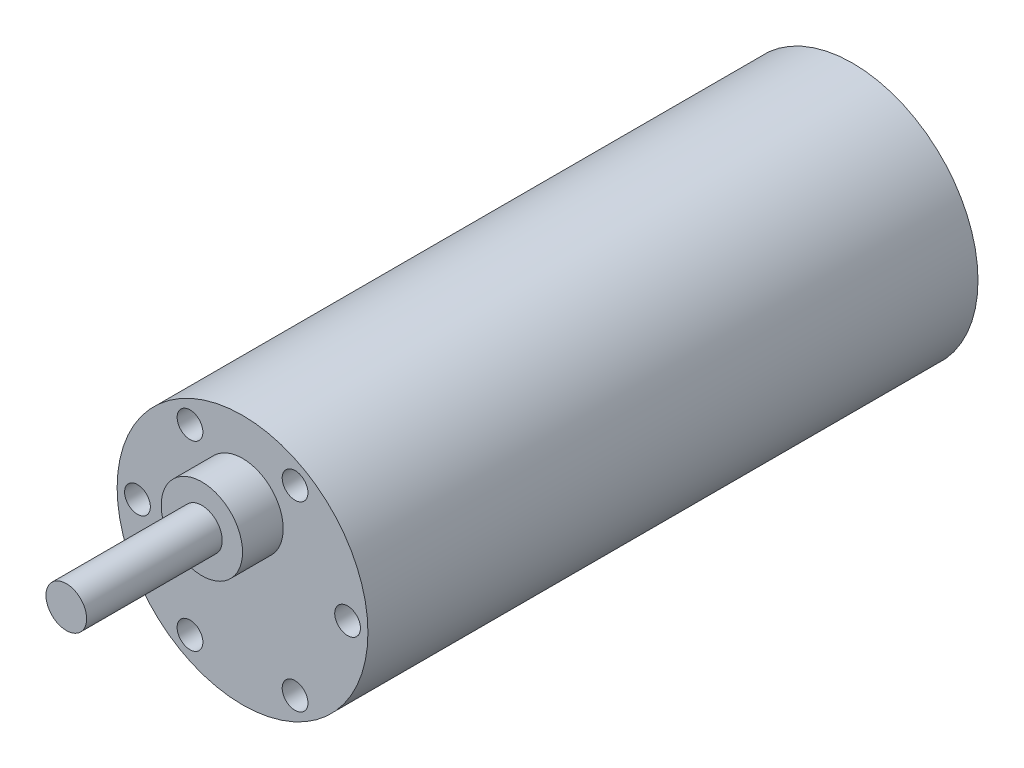
SolidWorks part; units mm, degrees
ref_plane "Front Plane" through (0, 0, 0) normal (1, 0, 0) x (0, 1, 0)
ref_plane "Top Plane" through (0, 0, 0) normal (0, 0, 1) x (0, 1, 0)
ref_plane "Right Plane" through (0, 0, 0) normal (0, 1, 0) x (-1, 0, 0)
sketch "Sketch1" plane through (0, 0, 0) normal (0, 0, 1) x (0, 1, 0)
  circle A0 centre (0, 0) radius 18.5
  dimension "D1" = 37
extrude "Boss-Extrude1" add sketch "Sketch1" along normal blind 90
sketch "Sketch2" plane through (0, 0, 90) normal (0, 0, 1) x (-1, 0, 0)
  circle A7 centre (0, -7) radius 6
  circle A9 centre (0, 0) radius 18.5 construction
  circle A21 centre (0, 0) radius 15.5 construction
  circle A22 centre (-15.5, 0) radius 1.9
  circle A23 centre (-7.75, 13.4234) radius 1.9
  circle A24 centre (7.75, 13.4234) radius 1.9
  circle A25 centre (15.5, 0) radius 1.9
  circle A26 centre (7.75, -13.4234) radius 1.9
  circle A27 centre (-7.75, -13.4234) radius 1.9
  point P0 (0, 0)
  point P19 (63.7281, -69.1924)
  point P20 (5.8781, 15.5086)
  point P21 (5.8781, 17.63)
  point P22 (63.7281, -69.1924)
  point P23 (5.8781, -12.0685)
  dimension "D2" = 37
  dimension "D14" = 31
  dimension "D15" = 3.8
  dimension "D6" = 12
  dimension "D13" = 7
  dimension "D16" = 6
extrude "Cut-Extrude1" cut sketch "Sketch2" against normal blind 3 contours A22 | A23 | A24 | A25 | A26 | A27 region at (15.5, 0, 90) region at (7.75, -13.4234, 90) region at (-7.75, -13.4234, 90) region at (-15.5, 0, 90) region at (-7.75, 13.4234, 90) region at (7.75, 13.4234, 90)
extrude "Boss-Extrude2" add sketch "Sketch2<3>" along normal blind 6 contours A7 region at (0, 7, 90)
sketch "Sketch2<3>" plane through (0, 0, 90) normal (0, 0, 1) x (-1, 0, 0) same geometry as "Sketch2"
sketch "Sketch3" plane through (0, 0, 96) normal (0, 0, 1) x (1, 0, 0)
  circle A0 centre (0, 7) radius 3
  dimension "D1" = 6
extrude "Boss-Extrude3" add sketch "Sketch3" along normal blind 20
